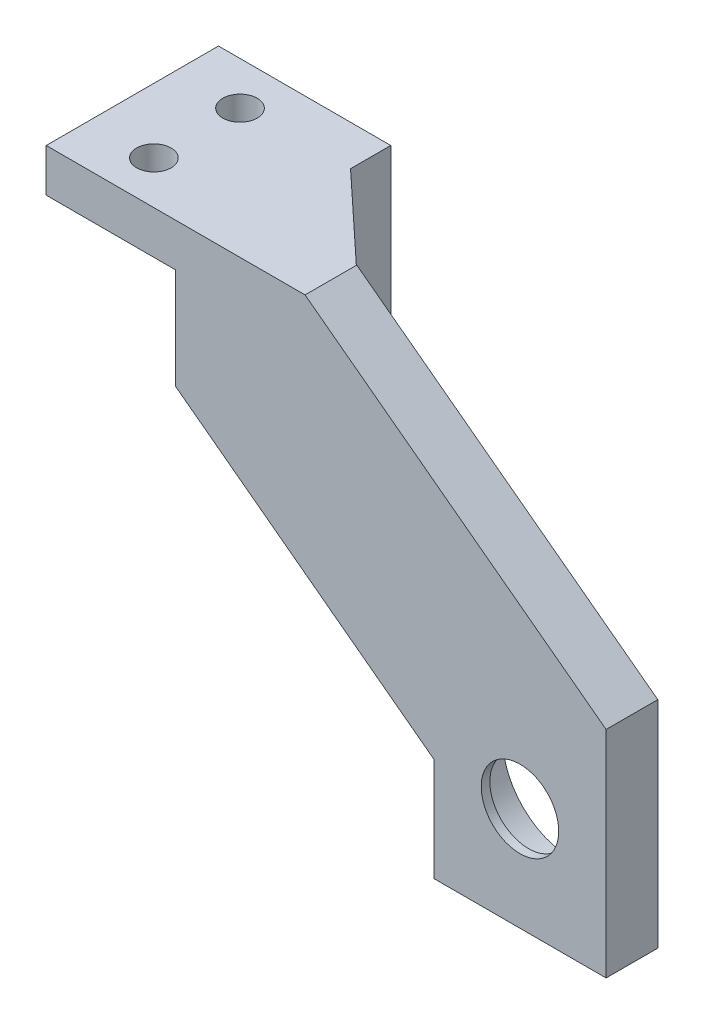
SolidWorks part; units mm, degrees
ref_plane "Front Plane" through (0, 0, 0) normal (0, 0, 1) x (1, 0, 0)
ref_plane "Top Plane" through (0, 0, 0) normal (0, 1, 0) x (1, 0, 0)
ref_plane "Right Plane" through (0, 0, 0) normal (1, 0, 0) x (0, 0, -1)
sketch "Sketch1" plane through (0, 0, 0) normal (0, 0, 1) x (1, 0, 0)
  circle A0 centre (0, 0) radius 4.5
  circle A1 centre (0, 0) radius 8
  circle A2 centre (0, 0) radius 10
  circle A3 centre (0, 0) radius 8 construction
  dimension "D1" = 9
  dimension "D2" = 20
extrude "Boss-Extrude1" add sketch "Sketch1" along normal blind 1 contours A2 A1 | A1 A0 region at (-7.7737, 0, 0) region at (-9.7172, 0, 0)
extrude "Boss-Extrude2" add sketch "Sketch1<4>" against normal up to surface (5 mm away) contours A2 A1 region at (-9.7172, 0, 0)
sketch "Sketch1<4>" plane through (0, 0, 0) normal (0, 0, 1) x (1, 0, 0) same geometry as "Sketch1"
sketch "Sketch2" plane through (0, 0, 1) normal (0, 0, 1) x (1, 0, 0)
  line L0 (-40, 22.5) -> (-10, 0)
  line L1 (-10, 0) -> (-10, -12)
  line L2 (-10, -12) -> (-10, 0) construction
  line L3 (-10, -12) -> (10, -12)
  line L4 (10, -12) -> (10, 34.2)
  line L5 (110, 34.2) -> (-290, 34.2) construction
  line L6 (10, 12.9884) -> (10, -12) construction
  line L7 (10, 34.2) -> (-40, 34.2)
  line L8 (-40, 34.2) -> (-40, 22.5)
  circle A0 centre (0, 0) radius 10 construction
  circle A1 centre (0, 0) radius 10
  circle M1 centre (0, 0) radius 10
extrude "Boss-Extrude3" add sketch "Sketch2" against normal up to surface (6 mm away) contours L7 L8 L0 L4 M1 | L3 L4 L1 M1 region at (-12.7734, 21.4272, 1) region at (0, -10.2332, 1) up to face at (10, 0, -5)
sketch "Sketch3" plane through (0, 34.2, 0) normal (0, 1, 0) x (1, 0, 0)
  line L0 (-40, -1) -> (-55, -1)
  line L1 (-55, -1) -> (-55, 19)
  line L2 (-55, 19) -> (-40, 19)
  line L3 (-40, -31) -> (-40, 269) construction
  line L4 (-40, 19) -> (-40, 5)
  line L5 (-55, 236) -> (-55, 256) construction
  line L6 (-40, 19) -> (-35, 19)
  line L7 (-35, 19) -> (-35, 5)
  line L8 (-40, 5) -> (10, 5) construction
  line L9 (-35, 14.33) -> (-25, 5)
  line L11 (-35, 236) -> (-35, 240.6667) construction
  line L13 (-40, 5) -> (10, 5)
  line L14 (-40, 5) -> (-40, -1)
  line L15 (-40, -1) -> (10, -1)
  line L16 (10, 5) -> (10, -1)
  line L17 (-40, 5) -> (10, -1) construction
  line L18 (-40, -1) -> (10, 5) construction
  point P21 (-15, 2)
  line M32 (-40, -31) -> (-40, 269)
  dimension "D1" = 0
  dimension "D2" = 4.67
  dimension "D3" = 0
extrude "Boss-Extrude4" add sketch "Sketch3" along normal up to surface (5 mm away) contours L2 L1 L0 M32 | L13 L7 L6 M32 | L7 L13 L9 | L16 L13 L15 M32 region at (-47.5, 34.2, -9) region at (-15, 34.2, -2) region at (-37.5, 34.2, -12) region at (-31.6667, 34.2, -8.11)
extrude "Boss-Extrude5" add sketch "Sketch3<4>" against normal up to surface (11.7 mm away) contours L13 L7 L6 M32 | L7 L13 L9 region at (-37.5, 34.2, -12) region at (-31.6667, 34.2, -8.11) up to face at (-25, 11.25, -2)
sketch "Sketch3<4>" plane through (0, 34.2, 0) normal (0, 1, 0) x (1, 0, 0) same geometry as "Sketch3"
sketch "Sketch4" plane through (0, 39.2, 0) normal (0, 1, 0) x (1, 0, 0)
  line L0 (-55, -1) -> (10, -1) construction
  line L1 (-55, 19) -> (-40, 19) construction
  line L2 (-55, 19) -> (-55, -1) construction
  line L3 (-55, -1) -> (-40, -1) construction
  line L4 (-40, 19) -> (-40, -1) construction
  line L5 (-55, 19) -> (-40, -1) construction
  line L6 (-55, -1) -> (-40, 19) construction
  line L8 (-40, -31) -> (-40, 269) construction
  line L9 (-55, 9) -> (-40, 9) construction
  circle A0 centre (-47.5, 14) radius 2
  circle A1 centre (-47.5, 14) radius 4 construction
  circle A3 centre (-47.5, 4) radius 4 construction
  circle A4 centre (-47.5, 4) radius 2
  point P4 (-47.5, 9)
  dimension "D1" = 4
  dimension "D2" = 8
  dimension "D3" = 5
  dimension "D4" = 7.5
extrude "Cut-Extrude1" cut sketch "Sketch4" against normal through all
sketch "Sketch5" plane through (0, 0, 1) normal (0, 0, 1) x (1, 0, 0)
  line L0 (0, 20.4884) -> (-24.9488, 39.2)
  line L2 (-40, 22.5) -> (-10, 0) construction
  line L3 (-55, 39.2) -> (10, 39.2) construction
  line L4 (0, 20.4884) -> (10, 12.9884)
  line L6 (10, -12) -> (10, 39.2) construction
  line L7 (-24.9488, 39.2) -> (10, 39.2)
  line L8 (10, 39.2) -> (10, 12.9884)
  dimension "D1" = 20.4884
  dimension "D2" = 0
extrude "Cut-Extrude2" cut sketch "Sketch5" against normal through all both and the other way through all
